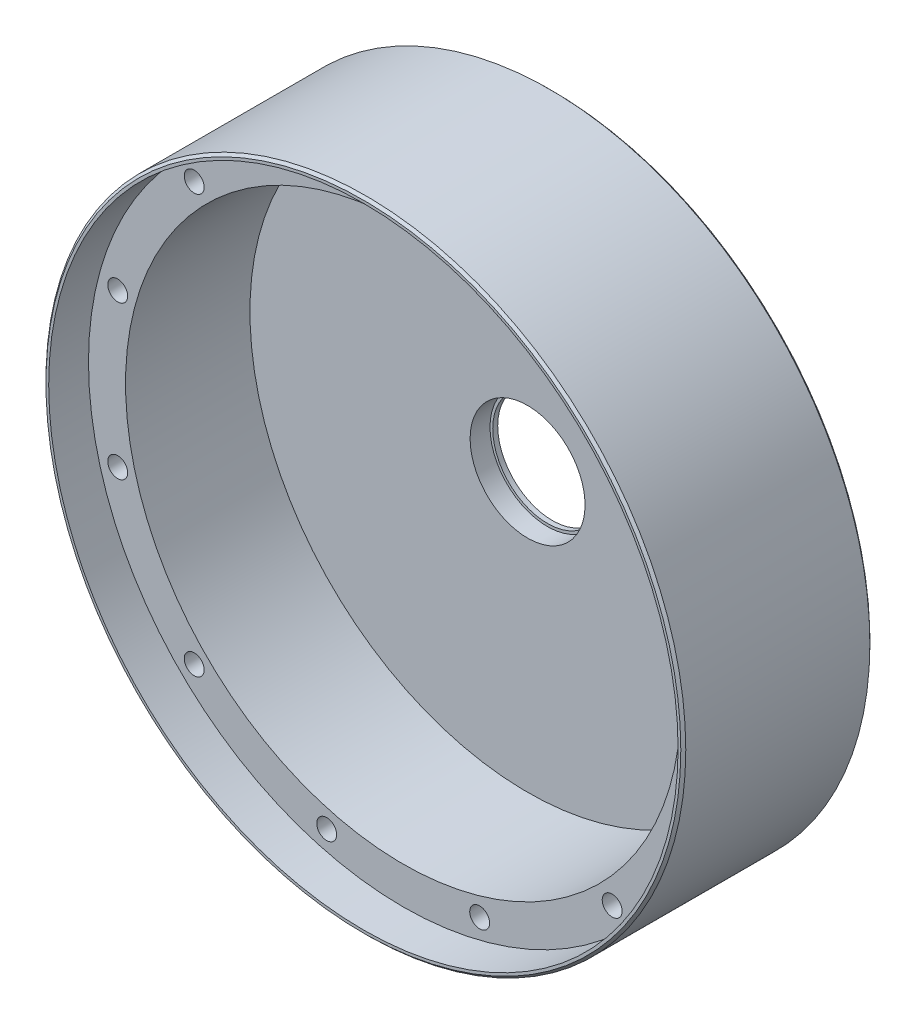
SolidWorks part; units mm, degrees
material "ABS"
ref_plane "Front Plane" through (0, 0, 0) normal (0, 0, 1) x (1, 0, 0)
ref_plane "Top Plane" through (0, 0, 0) normal (0, 1, 0) x (1, 0, 0)
ref_plane "Right Plane" through (0, 0, 0) normal (1, 0, 0) x (0, 0, -1)
sketch "Actuator Housing Mount" plane through (0, 0, 19) normal (0, 0, 1) x (1, 0, 0)
  line L0 (0, 0) -> (63, 0) construction
  line L1 (0, 0) -> (62.0607, 16.6291) construction
  circle A1 centre (57.376, 15.3739) radius 3.6 construction
  circle A2 centre (0, 0) radius 55.8
  circle A3 centre (57.376, 15.3739) radius 1.55
  circle A4 centre (57.376, -15.3739) radius 1.55
  circle A5 centre (42.0021, -42.0021) radius 1.55
  circle A6 centre (15.3739, -57.376) radius 1.55
  circle A7 centre (-15.3739, -57.376) radius 1.55
  circle A8 centre (-42.0021, -42.0021) radius 1.55
  circle A9 centre (-57.376, -15.3739) radius 1.55
  circle A10 centre (-57.376, 15.3739) radius 1.55
  circle A11 centre (-42.0021, 42.0021) radius 1.55
  circle A12 centre (-15.3739, 57.376) radius 1.55
  circle A13 centre (15.3739, 57.376) radius 1.55
  circle A14 centre (42.0021, 42.0021) radius 1.55
  circle A15 centre (0, 0) radius 64.3
  point P35 (0, 0)
extrude "Actuator Housing Wall" add sketch "Actuator Housing Mount" against normal blind 25
sketch "Sketch2" plane through (0, 0, -6) normal (0, 0, -1) x (-1, 0, 0)
  circle A0 centre (0, 0) radius 64.3
  circle A1 centre (0, 0) radius 64.3 construction
  circle M2 centre (-42.0021, 42.0021) radius 1.55
  circle M3 centre (-15.3739, 57.376) radius 1.55
  circle M4 centre (15.3739, 57.376) radius 1.55
  circle M5 centre (42.0021, 42.0021) radius 1.55
  circle M6 centre (57.376, 15.3739) radius 1.55
  circle M7 centre (57.376, -15.3739) radius 1.55
  circle M8 centre (42.0021, -42.0021) radius 1.55
  circle M9 centre (15.3739, -57.376) radius 1.55
  circle M10 centre (-15.3739, -57.376) radius 1.55
  circle M11 centre (-42.0021, -42.0021) radius 1.55
  circle M12 centre (0, 0) radius 55.8
  circle M13 centre (-57.376, -15.3739) radius 1.55
  circle M14 centre (-57.376, 15.3739) radius 1.55
  circle M15 centre (0, 0) radius 64.3
extrude "Boss-Extrude2" add sketch "Sketch2" along normal blind 5 contours M15 M3 M5 M7 M9 M11 M13 M14 M12 M10 M8 M6 M4 M2 | M12 region at (62.4813, 0, -6) region at (0, 0, -6)
sketch "Sketch3" plane through (0, 0, -11) normal (0, 0, -1) x (-1, 0, 0)
  circle A0 centre (0, 0) radius 11.55
  dimension "D1" = 23.1
extrude "Cut-Extrude1" cut sketch "Sketch3" along normal blind 4 from surface starting at face at (55.8, 0, -6)
sketch "Sketch4" plane through (0, 0, -11) normal (0, 0, -1) x (-1, 0, 0)
  circle A0 centre (0, 0) radius 11
  dimension "D1" = 22
extrude "Cut-Extrude2" cut sketch "Sketch4" against normal blind 4
sketch "Sketch6" plane through (0, 0, 19) normal (0, 0, 1) x (1, 0, 0)
  circle A0 centre (0, 0) radius 64.3
  circle A1 centre (0, 0) radius 63.25
  dimension "D1" = 128.6
  dimension "D2" = 126.5
extrude "Boss-Extrude3" add sketch "Sketch6" along normal blind 8
sketch "Sketch7" plane through (0, 0, 19) normal (0, 0, 1) x (1, 0, 0)
  circle A0 centre (57.376, -15.3739) radius 2
  circle A1 centre (42.0021, -42.0021) radius 2
  circle A2 centre (15.3739, -57.376) radius 2
  circle A3 centre (-15.3739, -57.376) radius 2
  circle A4 centre (-42.0021, -42.0021) radius 2
  circle A5 centre (-57.376, -15.3739) radius 2
  circle A6 centre (-57.376, 15.3739) radius 2
  circle A7 centre (-42.0021, 42.0021) radius 2
  circle A8 centre (-15.3739, 57.376) radius 2
  circle A9 centre (15.3739, 57.376) radius 2
  circle A10 centre (42.0021, 42.0021) radius 2
  circle A11 centre (57.376, 15.3739) radius 2
  point P27 (0, 0)
  dimension "D1" = 12
  dimension "M3 Insert" = 4
extrude "M3 Insert L12" cut sketch "Sketch7" against normal blind 12
chamfer "Chamfer2" distance 0.5 angle 45 2 edges at (64.3, 0, 27) (-64.3, 0, -11)
